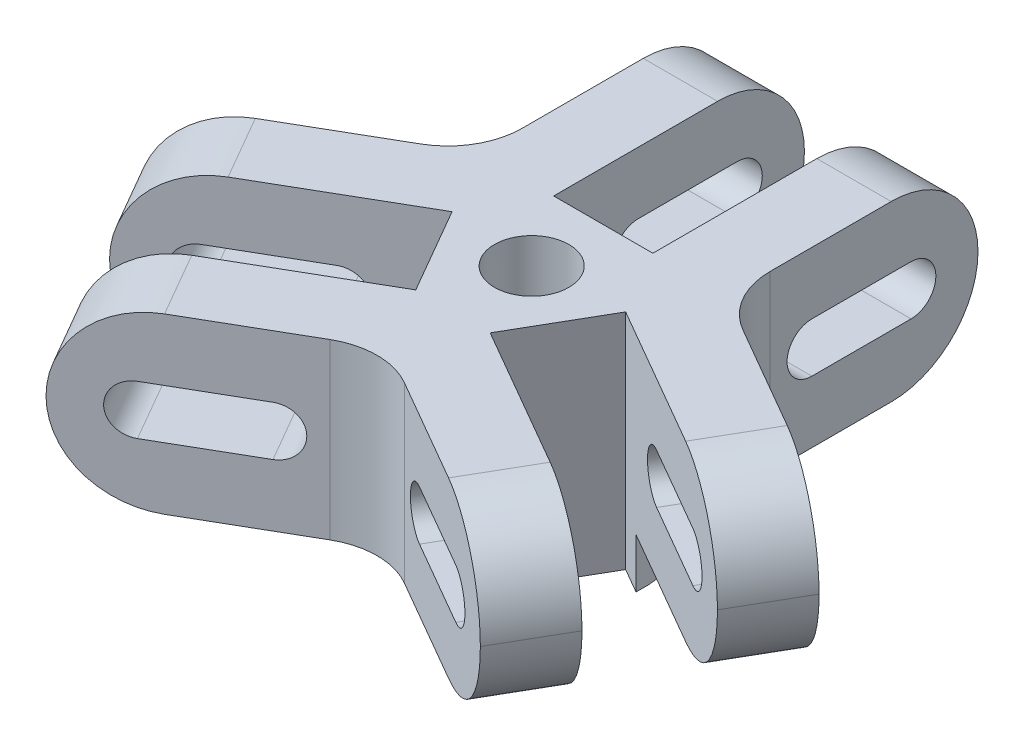
SolidWorks part; units mm, degrees
ref_plane "Front Plane" through (0, 0, 0) normal (0, 0, 1) x (1, 0, 0)
ref_plane "Top Plane" through (0, 0, 0) normal (0, 1, 0) x (1, 0, 0)
ref_plane "Right Plane" through (0, 0, 0) normal (1, 0, 0) x (0, 0, -1)
sketch "Sketch1" plane through (0, 0, 0) normal (0, 1, 0) x (1, 0, 0)
  line L1 (0, 28.8675) -> (-25, 14.4338) construction
  line L2 (-25, 14.4338) -> (-25, -14.4338) construction
  line L3 (-25, -14.4338) -> (0, -28.8675) construction
  line L4 (0, -28.8675) -> (25, -14.4338) construction
  line L5 (25, -14.4338) -> (25, 14.4338) construction
  line L6 (25, 14.4338) -> (0, 28.8675) construction
  line L9 (-5, 13) -> (5, 13)
  line L10 (13.7583, -2.1699) -> (8.7583, -10.8301)
  line L11 (-8.7583, -10.8301) -> (-13.7583, -2.1699)
  line L14 (5, 13) -> (5, 2.8868)
  line L23 (-5, 13) -> (-5, 2.8868)
  line L25 (8.7583, -10.8301) -> (0, -5.7735)
  line L27 (13.7583, -2.1699) -> (5, 2.8868)
  line L29 (-13.7583, -2.1699) -> (-5, 2.8868)
  line L31 (-8.7583, -10.8301) -> (0, -5.7735)
  circle A0 centre (0, 0) radius 25 construction
  circle A1 centre (0, 0) radius 1.5
  point P18 (0, 0)
  dimension "D1" = 50
  dimension "D4" = 3
  dimension "D2" = 10
  dimension "D7" = 13
  dimension "D3" = 3
extrude "Boss-Extrude1" add sketch "Sketch1" along normal mid plane 7
sketch "Sketch2" plane through (0, 0, 0) normal (1, 0, 0) x (0, 0, -1)
  line L1 (2.8868, -3.5) -> (2.8868, 3.5)
  line L2 (13, 3.5) -> (13, -3.5) construction
  line L3 (2.8868, 3.5) -> (2.8868, -3.5) construction
  line L4 (2.8868, 3.5) -> (13, 3.5)
  line L5 (13, 3.5) -> (13, -3.5)
  line L6 (13, -3.5) -> (2.8868, -3.5)
  dimension "D3" = 7
extrude "Cut-Extrude1" cut sketch "Sketch2" against normal mid plane 4 contours L4 L5 L6 L1
sketch "Sketch4" plane through (5, 0, 0) normal (1, 0, 0) x (0, 0, -1)
  line L0 (6.3, 0) -> (10.3, 0) construction
  line L1 (6.3, 1) -> (10.3, 1)
  line L2 (6.3, -1) -> (10.3, -1)
  line L3 (13, -3.5) -> (2.8868, -3.5) construction
  line L4 (13, 3.5) -> (13, -3.5) construction
  arc A0 (6.3, 1) -> (6.3, -1) centre (6.3, 0) ccw
  arc A1 (10.3, -1) -> (10.3, 1) centre (10.3, 0) ccw
  point P2 (8.3, 0)
  dimension "D1" = 1
  dimension "D2" = 4
  dimension "D3" = 8.3
extrude "Cut-Extrude3" cut sketch "Sketch4" against normal blind 13
fillet "Fillet2" radius 3 3 edges at (-5, 0, -2.8868) (5, 0, -2.8868) (0, 0, 5.7735)
pattern_circular "CirPattern1" count 3 over 360 about axis through (0, 0, 0) along (0, 1, 0) of "Cut-Extrude1", "Cut-Extrude3"
sketch "Sketch5" plane through (0, -3.5, 0) normal (0, -1, 0) x (1, 0, 0)
  line L21 (-1.5, 6.6395) -> (-8.7583, 10.8301)
  line L23 (-8.7583, 10.8301) -> (-10.2583, 8.2321)
  line L25 (-10.2583, 8.2321) -> (-1.5, 3.1754)
  line L27 (-13.7583, 2.1699) -> (-6.5, -2.0207)
  line L28 (-5, -4.6188) -> (-5, -13)
  line L30 (-2, -13) -> (-2, -2.8868)
  line L31 (-2, -2.8868) -> (2, -2.8868)
  line L32 (2, -2.8868) -> (2, -13)
  line L34 (5, -13) -> (5, -4.6188)
  line L35 (6.5, -2.0207) -> (13.7583, 2.1699)
  line L37 (-2.4911, 3.7476) -> (-1.5, 3.1754)
  line L38 (-1.5, 3.1754) -> (-3.5, -0.2887)
  line L39 (-1.5, 3.1754) -> (-3.5, -0.2887)
  line L41 (8.7583, 10.8301) -> (1.5, 6.6395)
  line L51 (-2, -4.0311) -> (-2, -2.8868)
  line L52 (-2, -2.8868) -> (2, -2.8868)
  line L53 (2, -2.8868) -> (2, -4.0311)
  line L63 (-3.5, -0.2887) -> (-12.2583, 4.7679)
  line L64 (-3.5, -0.2887) -> (-4.4911, 0.2835)
  line L65 (12.2583, 4.7679) -> (3.5, -0.2887)
  line L66 (4.4911, 0.2835) -> (3.5, -0.2887)
  line L67 (3.5, -0.2887) -> (1.5, 3.1754)
  line L68 (3.5, -0.2887) -> (1.5, 3.1754)
  line L69 (1.5, 3.1754) -> (10.2583, 8.2321)
  line L70 (1.5, 3.1754) -> (2.4911, 3.7476)
  line L71 (-12.2583, 4.7679) -> (-13.7583, 2.1699)
  line L73 (-5, -13) -> (-2, -13)
  line L75 (2, -13) -> (5, -13)
  line L77 (13.7583, 2.1699) -> (12.2583, 4.7679)
  line L79 (10.2583, 8.2321) -> (8.7583, 10.8301)
  arc A0 (-4.4911, 0.2835) -> (-2, -4.0311) centre (0, 0) ccw
  arc A1 (2.4911, 3.7476) -> (-2.4911, 3.7476) centre (0, 0) ccw
  arc A2 (2, -4.0311) -> (4.4911, 0.2835) centre (0, 0) ccw
  arc A7 (-5, -4.6188) -> (-6.5, -2.0207) centre (-8, -4.6188) ccw
  arc A9 (6.5, -2.0207) -> (5, -4.6188) centre (8, -4.6188) ccw
  arc A11 (-1.5, 6.6395) -> (1.5, 6.6395) centre (0, 9.2376) ccw
  dimension "D1" = 0
  dimension "D2" = 4.5
extrude "Boss-Extrude2" add sketch "Sketch5" along normal blind 2
fillet "Fillet3" radius 3.5 12 edges at (-9.5083, -3.5, 9.5311) (-9.5083, 3.5, 9.5311) (-13.0083, -3.5, 3.4689) (-13.0083, 3.5, 3.4689) (9.5083, -3.5, 9.5311) (9.5083, 3.5, 9.5311) (13.0083, -3.5, 3.4689) (13.0083, 3.5, 3.4689) (-3.5, -3.5, -13) (-3.5, 3.5, -13) (3.5, -3.5, -13) (3.5, 3.5, -13)
